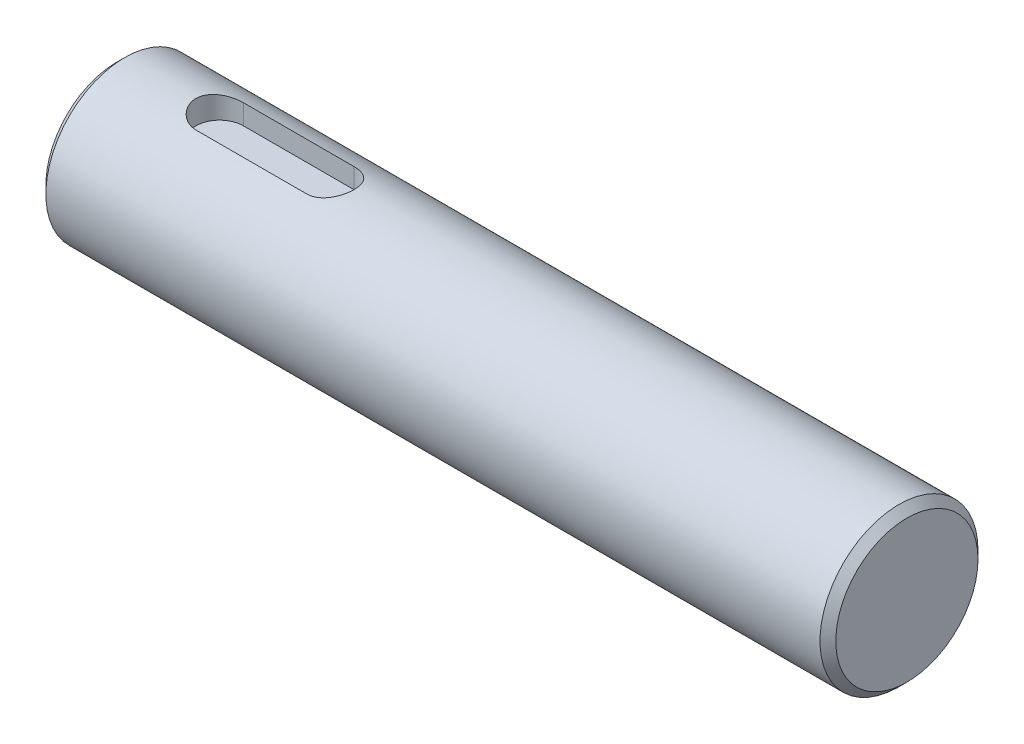
SolidWorks part; units mm, degrees
material "45"
ref_plane "前视基准面" through (0, 0, 0) normal (0, 0, 1) x (1, 0, 0)
ref_plane "上视基准面" through (0, 0, 0) normal (0, 1, 0) x (1, 0, 0)
ref_plane "右视基准面" through (0, 0, 0) normal (1, 0, 0) x (0, 0, -1)
ref_axis "基准轴1" through (88.99, 0, 0) along (-1, 0, 0)
sketch "草图1" plane through (0, 0, 0) normal (1, 0, 0) x (0, 0, -1)
  circle A0 centre (0, 0) radius 10
extrude "凸台-拉伸1" add sketch "草图1" along normal blind 100
ref_plane "基准面1" through (0, 10, 0) normal (0, 1, 0) x (1, 0, 0)
sketch "草图2" plane through (0, 10, 0) normal (0, 1, 0) x (1, 0, 0)
  line L0 (13, 3) -> (27, 3)
  line L1 (13, -3) -> (27, -3)
  arc A0 (13, 3) -> (13, -3) centre (13, 0) ccw
  arc A1 (27, 3) -> (27, -3) centre (27, 0) cw
  dimension "D1" = 3
  dimension "D2" = 14
extrude "切除-拉伸1" cut sketch "草图2" against normal blind 3
chamfer "倒角1" distance 1 angle 45 1 edges at (0, 0, -10)
chamfer "倒角2" distance 1 angle 45 1 edges at (100, 0, -10)
